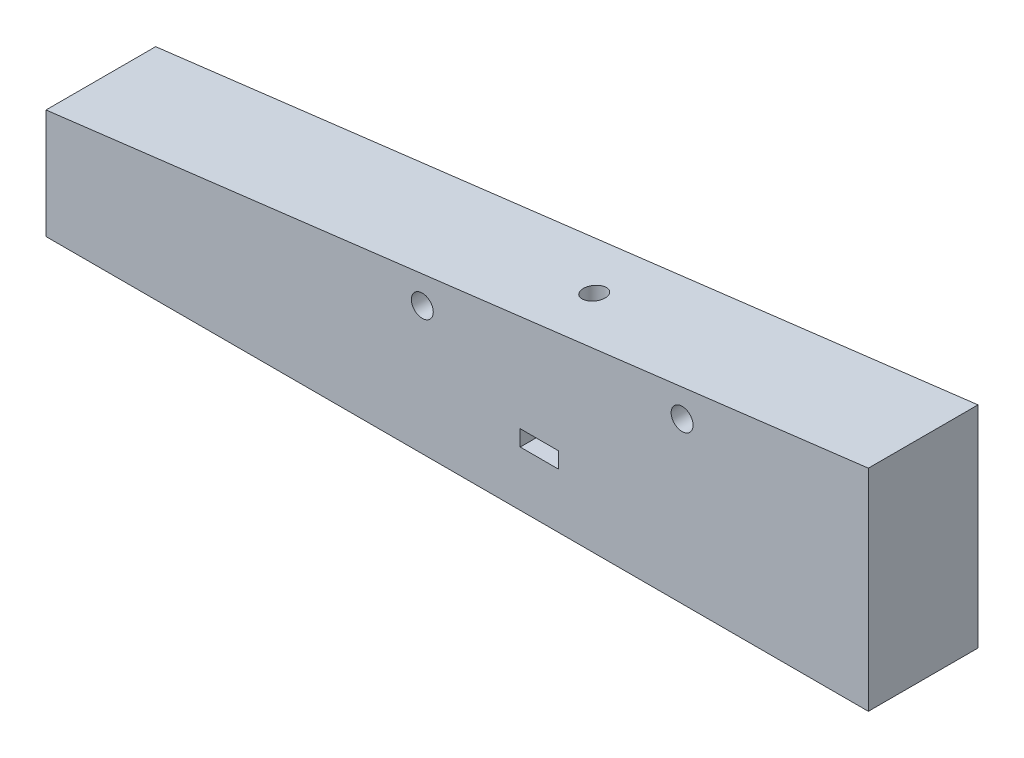
SolidWorks part; units mm, degrees
ref_plane "Front Plane" through (0, 0, 0) normal (0, 0, 1) x (1, 0, 0)
ref_plane "Top Plane" through (0, 0, 0) normal (0, 1, 0) x (1, 0, 0)
ref_plane "Right Plane" through (0, 0, 0) normal (1, 0, 0) x (0, 0, -1)
sketch "Sketch1" plane through (0, 0, 0) normal (0, 1, 0) x (1, 0, 0)
  line L1 (-75, -10) -> (75, -10)
  line L2 (-75, -10) -> (-75, 10)
  line L3 (-75, 10) -> (75, 10)
  line L4 (75, -10) -> (75, 10)
  line L5 (-75, -10) -> (75, 10) construction
  line L6 (-75, 10) -> (75, -10) construction
  point P0 (0, 0)
  dimension "D1" = 20
  dimension "D2" = 150
extrude "Boss-Extrude1" add sketch "Sketch1" along normal mid plane 20
sketch "Sketch2" plane through (0, 0, 0) normal (0, 0, 1) x (1, 0, 0)
  line L0 (-75, 10) -> (75, 10)
  line L1 (75, 10) -> (75, 28.4177)
  line L2 (75, 28.4177) -> (-75, 10)
  dimension "D1" = 7
extrude "Boss-Extrude2" add sketch "Sketch2" along normal mid plane 20
sketch "Sketch4" plane through (0, -10, 0) normal (0, -1, 0) x (1, 0, 0)
  line L0 (21.1297, 0) -> (-21.1297, 0) construction
  line L1 (0, -11) -> (0, 11) construction
  circle A0 centre (15, 0) radius 2
  dimension "D1" = 4
  dimension "D2" = 15
extrude "Cut-Extrude1" cut sketch "Sketch4" against normal through all both
sketch "Sketch5" plane through (0, 0, 10) normal (0, 0, 1) x (1, 0, 0)
  line L1 (11.5, 0) -> (18.5, 0)
  line L2 (11.5, 0) -> (11.5, 2.9)
  line L3 (11.5, 2.9) -> (18.5, 2.9)
  line L4 (18.5, 0) -> (18.5, 2.9)
  line L5 (11.5, 0) -> (18.5, 2.9) construction
  line L6 (11.5, 2.9) -> (18.5, 0) construction
  line L10 (-75, -10) -> (75, -10) construction
  line L11 (40.4161, 24.1713) -> (41.0255, 19.2086) construction
  line L12 (75, 28.4177) -> (-75, 10) construction
  line L13 (-6.9705, 18.353) -> (-6.3611, 13.3902) construction
  line L14 (0, -11) -> (0, 11) construction
  circle A0 centre (-6.3611, 13.3902) radius 2
  circle A1 centre (41.0255, 19.2086) radius 2
  point P0 (15, 1.45)
  point P17 (0, 0)
  dimension "D9" = 4
  dimension "D10" = 4
  dimension "D1" = 2.9
  dimension "D2" = 7
  dimension "D3" = 15
  dimension "D4" = 10
  dimension "D5" = 5
  dimension "D6" = 90
  dimension "D7" = 5
  dimension "D8" = 90
extrude "Cut-Extrude2" cut sketch "Sketch5" against normal through all both contours A1 | A0 region at (-6.3611, 13.3902, 10) region at (41.0255, 19.2086, 10)
extrude "Cut-Extrude3" cut sketch "Sketch5<3>" against normal blind 13.8 contours L3 L4 L1 L2
sketch "Sketch5<3>" plane through (0, 0, 10) normal (0, 0, 1) x (1, 0, 0) same geometry as "Sketch5"
